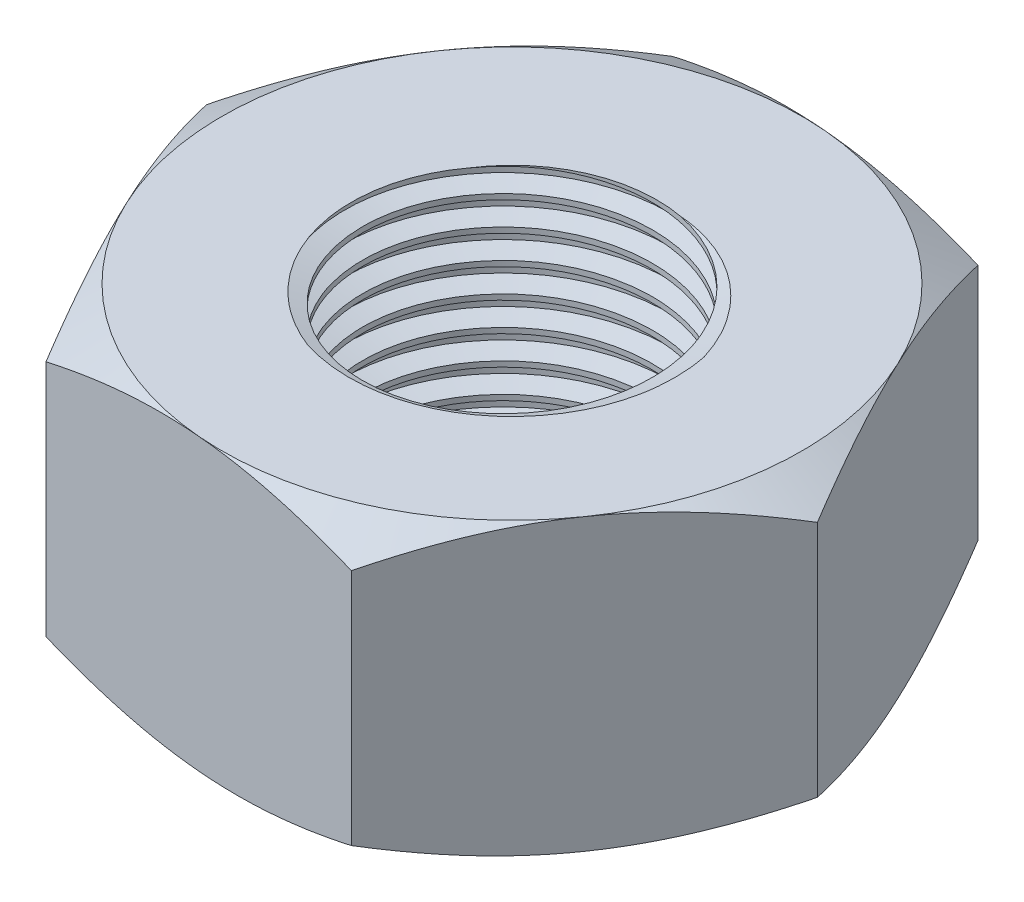
SolidWorks part; units mm, degrees
ref_plane "Front Plane" through (0, 0, 0) normal (0, 0, 1) x (1, 0, 0)
ref_plane "Top Plane" through (0, 0, 0) normal (0, 1, 0) x (1, 0, 0)
ref_plane "Right Plane" through (0, 0, 0) normal (1, 0, 0) x (0, 0, -1)
sketch "Sketch1" plane through (0, 0, 0) normal (0, 1, 0) x (1, 0, 0)
  line L1 (-4.9109, 10.4507) -> (-11.506, 0.9724)
  line L2 (-11.506, 0.9724) -> (-6.5951, -9.4783)
  line L3 (-6.5951, -9.4783) -> (4.9109, -10.4507)
  line L4 (4.9109, -10.4507) -> (11.506, -0.9724)
  line L5 (11.506, -0.9724) -> (6.5951, 9.4783)
  line L6 (6.5951, 9.4783) -> (-4.9109, 10.4507)
  circle A0 centre (0, 0) radius 10 construction
extrude "Boss-Extrude1" add sketch "Sketch1" along normal blind 10
sketch "Sketch2" plane through (0, 10, 0) normal (0, 1, 0) x (1, 0, 0)
  circle A0 centre (0, 0) radius 22.7605
  circle A1 centre (0, 0) radius 10
extrude "Cut-Extrude8" cut sketch "Sketch2" against normal blind 2 draft 60
ref_plane "Plane2" through (0, 5, 0) normal (0, 1, 0) x (1, 0, 0)
mirror "Mirror2" about plane through (0, 5, 0) normal (0, 1, 0) of "Cut-Extrude8"
sketch "Sketch4" plane through (0, 10, 0) normal (0, 1, 0) x (1, 0, 0)
  circle A0 centre (0, 0) radius 5
extrude "Cut-Extrude9" cut sketch "Sketch4" against normal blind 20
ref_plane "Plane3" through (0, 11, 0) normal (0, 1, 0) x (1, 0, 0)
sketch "Sketch5" plane through (0, 11, 0) normal (0, 1, 0) x (1, 0, 0)
  circle A0 centre (0, 0) radius 5
curve "Helix/Spiral1" pitch 1 height 17 radius 5 centre (0, 11, 0) axis (0, -1, 0) start towards (0, 0, 1)
sketch "Sketch6" plane through (0, 0, 0) normal (1, 0, 0) x (0, 0, -1)
  line L0 (4.9674, 10.8569) -> (4.9674, 10.0182)
  line L1 (4.9674, 10.0182) -> (5.6158, 10.2184)
  line L2 (5.6158, 10.2184) -> (5.6158, 10.5487)
  line L3 (5.6158, 10.5487) -> (4.9674, 10.8569)
  spline S0 degree 3 poles (3.5355, 11) (3.997, 10.9792) (4.7448, 10.9372) (5.1308, 10.8746) (4.7321, 10.8118) (3.6072, 10.7491) (1.9292, 10.6863) (-0.0446, 10.6236) (-2.0116, 10.5609) (-3.6701, 10.4982) (-4.7658, 10.4354) (-5.1306, 10.3727) (-4.7087, 10.31) (-3.5646, 10.2472) (-1.874, 10.1845) (0.1041, 10.1218) (2.0662, 10.059) (3.7114, 9.9963) (4.7875, 9.9336) (5.1294, 9.8708) (4.6847, 9.8081) (3.5216, 9.7454) (1.8185, 9.6827) (-0.1636, 9.6199) (-2.1205, 9.5572) (-3.7522, 9.4945) (-4.8086, 9.4317) (-5.1275, 9.369) (-4.6601, 9.3063) (-3.4781, 9.2435) (-1.7627, 9.1808) (0.223, 9.1181) (2.1745, 9.0554) (3.7926, 8.9926) (4.829, 8.9299) (5.1249, 8.8672) (4.6349, 8.8044) (3.4341, 8.7417) (1.7067, 8.679) (-0.2824, 8.6162) (-2.2282, 8.5535) (-3.8324, 8.4908) (-4.8488, 8.428) (-5.1216, 8.3653) (-4.6091, 8.3026) (-3.3897, 8.2399) (-1.6505, 8.1771) (0.3418, 8.1144) (2.2817, 8.0517) (3.8717, 7.9889) (4.8679, 7.9262) (5.1177, 7.8635) (4.5826, 7.8007) (3.3448, 7.738) (1.5941, 7.6753) (-0.4011, 7.6125) (-2.3348, 7.5498) (-3.9104, 7.4871) (-4.8864, 7.4244) (-5.113, 7.3616) (-4.5556, 7.2989) (-3.2995, 7.2362) (-1.5374, 7.1734) (0.4604, 7.1107) (2.3876, 7.048) (3.9487, 6.9852) (4.9042, 6.9225) (5.1077, 6.8598) (4.5279, 6.797) (3.2537, 6.7343) (1.4806, 6.6716) (-0.5196, 6.6089) (-2.4401, 6.5461) (-3.9864, 6.4834) (-4.9214, 6.4207) (-5.1017, 6.3579) (-4.4996, 6.2952) (-3.2075, 6.2325) (-1.4235, 6.1697) (0.5787, 6.107) (2.4923, 6.0443) (4.0236, 5.9815) (4.9379, 5.9188) (5.095, 5.8561) (4.4707, 5.7934) (3.1609, 5.7306) (1.3663, 5.6679) (-0.6378, 5.6052) (-2.5441, 5.5424) (-4.0602, 5.4797) (-4.9537, 5.417) (-5.0876, 5.3542) (-4.4412, 5.2915) (-3.1138, 5.2288) (-1.3089, 5.1661) (0.6968, 5.1033) (2.5956, 5.0406) (4.0963, 4.9779) (4.9689, 4.9151) (5.0795, 4.8524) (4.4111, 4.7897) (3.0663, 4.7269) (1.2513, 4.6642) (-0.7557, 4.6015) (-2.6467, 4.5387) (-4.1319, 4.476) (-4.9834, 4.4133) (-5.0707, 4.3506) (-4.3805, 4.2878) (-3.0184, 4.2251) (-1.1935, 4.1624) (0.8144, 4.0996) (2.6975, 4.0369) (4.1669, 3.9742) (4.9972, 3.9114) (5.0613, 3.8487) (4.3492, 3.786) (2.9701, 3.7232) (1.1356, 3.6605) (-0.8731, 3.5978) (-2.7479, 3.5351) (-4.2013, 3.4723) (-5.0104, 3.4096) (-5.0512, 3.3469) (-4.3173, 3.2841) (-2.9214, 3.2214) (-1.0775, 3.1587) (0.9317, 3.0959) (2.7979, 3.0332) (4.2352, 2.9705) (5.0229, 2.9077) (5.0404, 2.845) (4.2849, 2.7823) (2.8723, 2.7196) (1.0193, 2.6568) (-0.9901, 2.5941) (-2.8476, 2.5314) (-4.2685, 2.4686) (-5.0347, 2.4059) (-5.0289, 2.3432) (-4.2519, 2.2804) (-2.8228, 2.2177) (-0.9609, 2.155) (1.0484, 2.0923) (2.8969, 2.0295) (4.3012, 1.9668) (5.0459, 1.9041) (5.0167, 1.8413) (4.2183, 1.7786) (2.773, 1.7159) (0.9024, 1.6531) (-1.1065, 1.5904) (-2.9458, 1.5277) (-4.3333, 1.4649) (-5.0563, 1.4022) (-5.0039, 1.3395) (-4.1841, 1.2768) (-2.7227, 1.214) (-0.8438, 1.1513) (1.1646, 1.0886) (2.9943, 1.0258) (4.3649, 0.9631) (5.0661, 0.9004) (4.9904, 0.8376) (4.1494, 0.7749) (2.6721, 0.7122) (0.7851, 0.6494) (-1.2224, 0.5867) (-3.0424, 0.524) (-4.3959, 0.4613) (-5.0752, 0.3985) (-4.9762, 0.3358) (-4.1142, 0.2731) (-2.6212, 0.2103) (-0.7262, 0.1476) (1.2801, 0.0849) (3.0901, 0.0221) (4.4263, -0.0406) (5.0836, -0.1033) (4.9614, -0.1661) (4.0783, -0.2288) (2.5699, -0.2915) (0.6673, -0.3542) (-1.3376, -0.417) (-3.1374, -0.4797) (-4.456, -0.5424) (-5.0914, -0.6052) (-4.9459, -0.6679) (-4.042, -0.7306) (-2.5182, -0.7934) (-0.6083, -0.8561) (1.3949, -0.9188) (3.1842, -0.9815) (4.4852, -1.0443) (5.0984, -1.107) (4.9297, -1.1697) (4.0051, -1.2325) (2.4662, -1.2952) (0.5492, -1.3579) (-1.4521, -1.4207) (-3.2307, -1.4834) (-4.5138, -1.5461) (-5.1048, -1.6089) (-4.9129, -1.6716) (-3.9676, -1.7343) (-2.4139, -1.797) (-0.49, -1.8598) (1.509, -1.9225) (3.2767, -1.9852) (4.5418, -2.048) (5.1105, -2.1107) (4.8954, -2.1734) (3.9296, -2.2362) (2.3612, -2.2989) (0.4307, -2.3616) (-1.5658, -2.4244) (-3.3222, -2.4871) (-4.5692, -2.5498) (-5.1154, -2.6125) (-4.8772, -2.6753) (-3.8911, -2.738) (-2.3083, -2.8007) (-0.3714, -2.8635) (1.6223, -2.9262) (3.3673, -2.9889) (4.5959, -3.0517) (5.1198, -3.1144) (4.8584, -3.1771) (3.8521, -3.2399) (2.255, -3.3026) (0.3121, -3.3653) (-1.6787, -3.428) (-3.412, -3.4908) (-4.6221, -3.5535) (-5.1234, -3.6162) (-4.839, -3.679) (-3.8125, -3.7417) (-2.2014, -3.8044) (-0.2527, -3.8672) (1.7348, -3.9299) (3.4562, -3.9926) (4.6476, -4.0554) (5.1263, -4.1181) (4.8189, -4.1808) (3.7725, -4.2435) (2.1475, -4.3063) (0.1933, -4.369) (-1.7906, -4.4317) (-3.4999, -4.4945) (-4.6725, -4.5572) (-5.1285, -4.6199) (-4.7981, -4.6827) (-3.7319, -4.7454) (-2.0934, -4.8081) (-0.1338, -4.8708) (1.8462, -4.9336) (3.5432, -4.9963) (4.6968, -5.059) (5.1301, -5.1218) (4.7767, -5.1845) (3.6908, -5.2472) (2.0389, -5.31) (0.0744, -5.3727) (-1.9016, -5.4354) (-3.586, -5.4982) (-4.7204, -5.5609) (-5.1309, -5.6236) (-4.7547, -5.6863) (-3.6492, -5.7491) (-1.9843, -5.8118) (-0.0145, -5.8746) (1.9554, -5.9372) (3.074, -5.9792) (3.5355, -6) knots 0 0 0 0 0.00369 0.00738 0.01107 0.01476 0.01845 0.02214 0.02583 0.02952 0.03321 0.0369 0.04059 0.04428 0.04797 0.051661 0.055351 0.059041 0.062731 0.066421 0.070111 0.073801 0.077491 0.081181 0.084871 0.088561 0.092251 0.095941 0.099631 0.103321 0.107011 0.110701 0.114391 0.118081 0.121771 0.125461 0.129151 0.132841 0.136531 0.140221 0.143911 0.147601 0.151292 0.154982 0.158672 0.162362 0.166052 0.169742 0.173432 0.177122 0.180812 0.184502 0.188192 0.191882 0.195572 0.199262 0.202952 0.206642 0.210332 0.214022 0.217712 0.221402 0.225092 0.228782 0.232472 0.236162 0.239852 0.243542 0.247232 0.250923 0.254613 0.258303 0.261993 0.265683 0.269373 0.273063 0.276753 0.280443 0.284133 0.287823 0.291513 0.295203 0.298893 0.302583 0.306273 0.309963 0.313653 0.317343 0.321033 0.324723 0.328413 0.332103 0.335793 0.339483 0.343173 0.346863 0.350554 0.354244 0.357934 0.361624 0.365314 0.369004 0.372694 0.376384 0.380074 0.383764 0.387454 0.391144 0.394834 0.398524 0.402214 0.405904 0.409594 0.413284 0.416974 0.420664 0.424354 0.428044 0.431734 0.435424 0.439114 0.442804 0.446494 0.450185 0.453875 0.457565 0.461255 0.464945 0.468635 0.472325 0.476015 0.479705 0.483395 0.487085 0.490775 0.494465 0.498155 0.501845 0.505535 0.509225 0.512915 0.516605 0.520295 0.523985 0.527675 0.531365 0.535055 0.538745 0.542435 0.546125 0.549815 0.553506 0.557196 0.560886 0.564576 0.568266 0.571956 0.575646 0.579336 0.583026 0.586716 0.590406 0.594096 0.597786 0.601476 0.605166 0.608856 0.612546 0.616236 0.619926 0.623616 0.627306 0.630996 0.634686 0.638376 0.642066 0.645756 0.649446 0.653137 0.656827 0.660517 0.664207 0.667897 0.671587 0.675277 0.678967 0.682657 0.686347 0.690037 0.693727 0.697417 0.701107 0.704797 0.708487 0.712177 0.715867 0.719557 0.723247 0.726937 0.730627 0.734317 0.738007 0.741697 0.745387 0.749077 0.752768 0.756458 0.760148 0.763838 0.767528 0.771218 0.774908 0.778598 0.782288 0.785978 0.789668 0.793358 0.797048 0.800738 0.804428 0.808118 0.811808 0.815498 0.819188 0.822878 0.826568 0.830258 0.833948 0.837638 0.841328 0.845018 0.848708 0.852399 0.856089 0.859779 0.863469 0.867159 0.870849 0.874539 0.878229 0.881919 0.885609 0.889299 0.892989 0.896679 0.900369 0.904059 0.907749 0.911439 0.915129 0.918819 0.922509 0.926199 0.929889 0.933579 0.937269 0.940959 0.944649 0.948339 0.95203 0.95572 0.95941 0.9631 0.96679 0.97048 0.97417 0.97786 0.98155 0.98524 0.98893 0.99262 0.99631 1 1 1 1 construction
sweep "Cut-Sweep1" cut profiles "Sketch6" path "Helix/Spiral1" align with end faces yes
